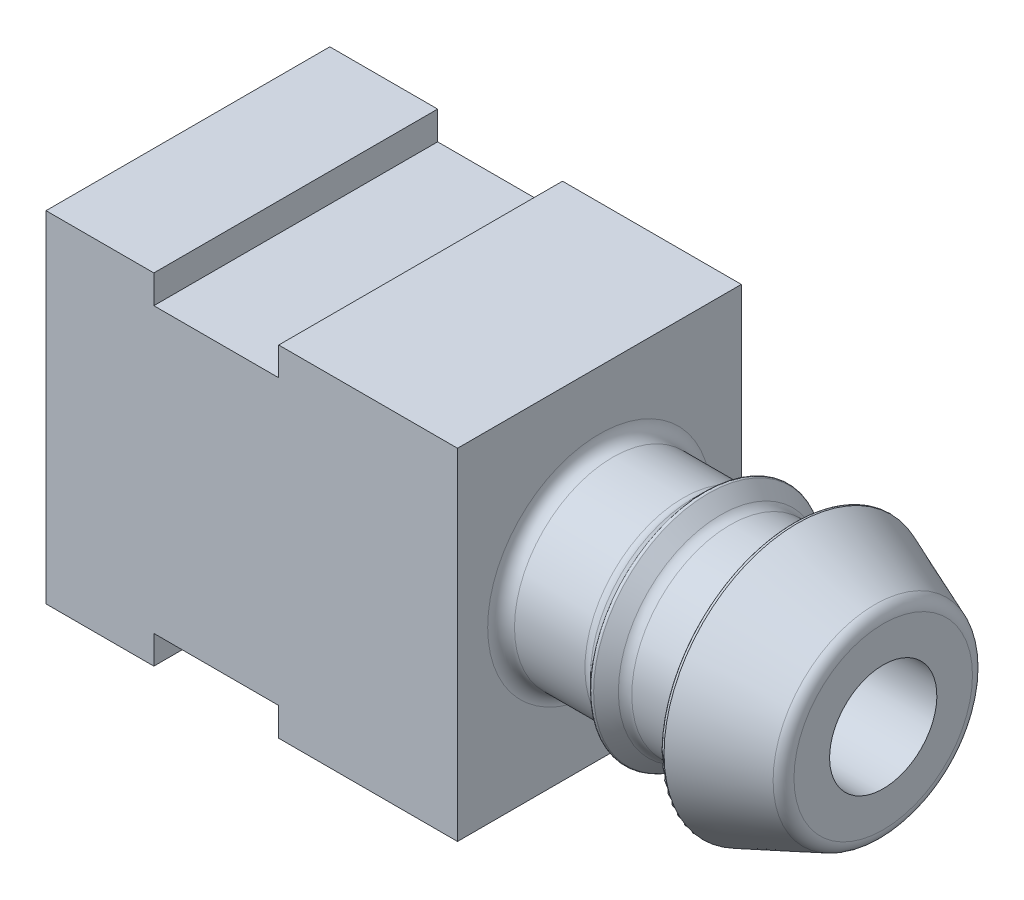
SolidWorks part; units mm, degrees
ref_plane "Front Plane" through (0, 0, 0) normal (0, 0, 1) x (1, 0, 0)
ref_plane "Top Plane" through (0, 0, 0) normal (0, 1, 0) x (1, 0, 0)
ref_plane "Right Plane" through (0, 0, 0) normal (1, 0, 0) x (0, 0, -1)
sketch "Sketch2" plane through (0, 0, 0) normal (0, 1, 0) x (1, 0, 0)
  line L0 (0, -6.35) -> (0, 6.35)
  line L1 (0, 6.35) -> (-18.415, 6.35)
  line L2 (-18.415, 6.35) -> (-18.415, -6.35)
  line L3 (-18.415, -6.35) -> (0, -6.35)
  circle A0 centre (-12.7, 0) radius 3.175
  point P4 (0, 0)
  point P10 (-18.415, 0)
  dimension "D3" = 6.35
  dimension "D4" = 5.715
  dimension "D1" = 12.7
  dimension "D2" = 12.7
extrude "Boss-Extrude2" add sketch "Sketch2" along normal mid plane 12.7
hole_wizard "#10-32 Tapped Hole1" positions "Sketch4" profile "Sketch5" tap size "#10-32" standard "ANSI Inch"
sketch "Sketch4" plane through (0, 0, -6.35) normal (0, 0, -1) x (-1, 0, 0)
  line L0 (0, 6.35) -> (0, -6.35) construction
  point P15 (4.8, 0)
  point P20 (0, 0)
  dimension "D1" = 4.8
sketch "Sketch5" plane through (-4.8, 0, -6.35) normal (1, 0, 0) x (0, 1, 0)
  line L0 (0, 0) -> (0, 8.3253)
  line L1 (0, 8.3253) -> (2.0193, 7.112)
  line L2 (2.0193, 7.112) -> (2.0193, 0)
  line L5 (2.0193, 0) -> (0, 0)
  line L10 (0, 8.3253) -> (-2.0193, 7.112) construction
  line L11 (0, -6.35) -> (0, 107.95) construction
  dimension "Tap Drill Dia." = 4.0386
  dimension "Tap Drill Depth" = 7.112
  dimension "Drill Angle" = 118
cosmetic thread "Hole Thread1" parameters "D1"=6.35, "D2"=4.826
sketch "Sketch3" plane through (0, 0, 0) normal (0, 0, 1) x (1, 0, 0)
  line L1 (0, 6.35) -> (0, -6.35) construction
  line L4 (0, 0) -> (0, 4.4)
  line L13 (12.7, 4.4) -> (12.7, 0)
  line L14 (12.7, 0) -> (0, 0)
  line L15 (12.7, 4.4) -> (8.7, 6)
  line L16 (8.7, 6) -> (8.7, 4.4)
  line L23 (0, 4.4) -> (4, 4.4)
  line L25 (5.6, 4.4) -> (4.8, 5.2)
  line L26 (4.8, 5.2) -> (4, 4.4)
  line L27 (5.6, 4.4) -> (8.7, 4.4)
  line L29 (4.8, 5.2) -> (4.8, 4.4) construction
  line L30 (5.6, 4.4) -> (4.8, 4.4) construction
  point P4 (7.24, 10.75)
  point P10 (7.2438, 10.75)
  point P14 (4.8, 4.4)
  dimension "D1" = 12.7
  dimension "D2" = 4.4
  dimension "D3" = 4
  dimension "D4" = 1.6
  dimension "D5" = 7.9
  dimension "D6" = 0.8
revolve "Revolve1" add sketch "Sketch3" angle 360 about L14
sketch "Sketch18" plane through (12.7, 0, 0) normal (1, 0, 0) x (0, 0, -1)
  circle A0 centre (0, 0) radius 2.4
  dimension "D1" = 4.8
extrude "Cut-Extrude2" cut sketch "Sketch18" against normal blind 20.6
sketch "Sketch12" plane through (0, -6.35, 0) normal (0, -1, 0) x (1, 0, 0)
  circle A0 centre (-12.7, 0) radius 3.175
extrude "Boss-Extrude3" add sketch "Sketch12" against normal blind 12.7
sketch "Sketch13" plane through (0, -6.35, 0) normal (0, -1, 0) x (1, 0, 0)
  line L1 (0, 6.35) -> (-18.415, 6.35)
  line L2 (0, 6.35) -> (0, -6.35)
  line L3 (0, -6.35) -> (-18.415, -6.35)
  line L4 (-18.415, 6.35) -> (-18.415, -6.35)
extrude "Boss-Extrude4" add sketch "Sketch13" along normal blind 1.27
sketch "Sketch14" plane through (0, 6.35, 0) normal (0, 1, 0) x (1, 0, 0)
  line L1 (-18.415, -6.35) -> (0, -6.35)
  line L2 (-18.415, -6.35) -> (-18.415, 6.35)
  line L3 (-18.415, 6.35) -> (0, 6.35)
  line L4 (0, -6.35) -> (0, 6.35)
extrude "Boss-Extrude5" add sketch "Sketch14" along normal blind 1.27
sketch "Sketch15" plane through (0, 0, -6.35) normal (0, 0, -1) x (-1, 0, 0)
  line L0 (0, 7.62) -> (18.415, 7.62) construction
  line L1 (8.001, 7.62) -> (13.589, 7.62)
  line L2 (8.001, 7.62) -> (8.001, 6.35)
  line L3 (8.001, 6.35) -> (13.589, 6.35)
  line L4 (13.589, 7.62) -> (13.589, 6.35)
  line L10 (18.415, 7.62) -> (18.415, -7.62) construction
  line L11 (0, 0) -> (50000, 0) construction
  line L12 (13.589, -7.62) -> (13.589, -6.35)
  line L13 (8.001, -6.35) -> (13.589, -6.35)
  line L14 (8.001, -7.62) -> (8.001, -6.35)
  line L15 (8.001, -7.62) -> (13.589, -7.62)
  point P8 (18.415, 0)
  point P14 (8.001, 6.985)
  dimension "D1" = 1.27
  dimension "D3" = 4.826
  dimension "D4" = 5.588
extrude "Cut-Extrude1" cut sketch "Sketch15" against normal through all
fillet "Fillet1" radius 0.1 2 edges at (4.8, 5.2, 0) (8.7, 6, 0)
fillet "Fillet2" radius 0.6 5 edges at (8.7, 4.4, 0) (5.6, 4.4, 0) (4, 4.4, 0) (0, 4.4, 0) (12.7, 4.4, 0)
